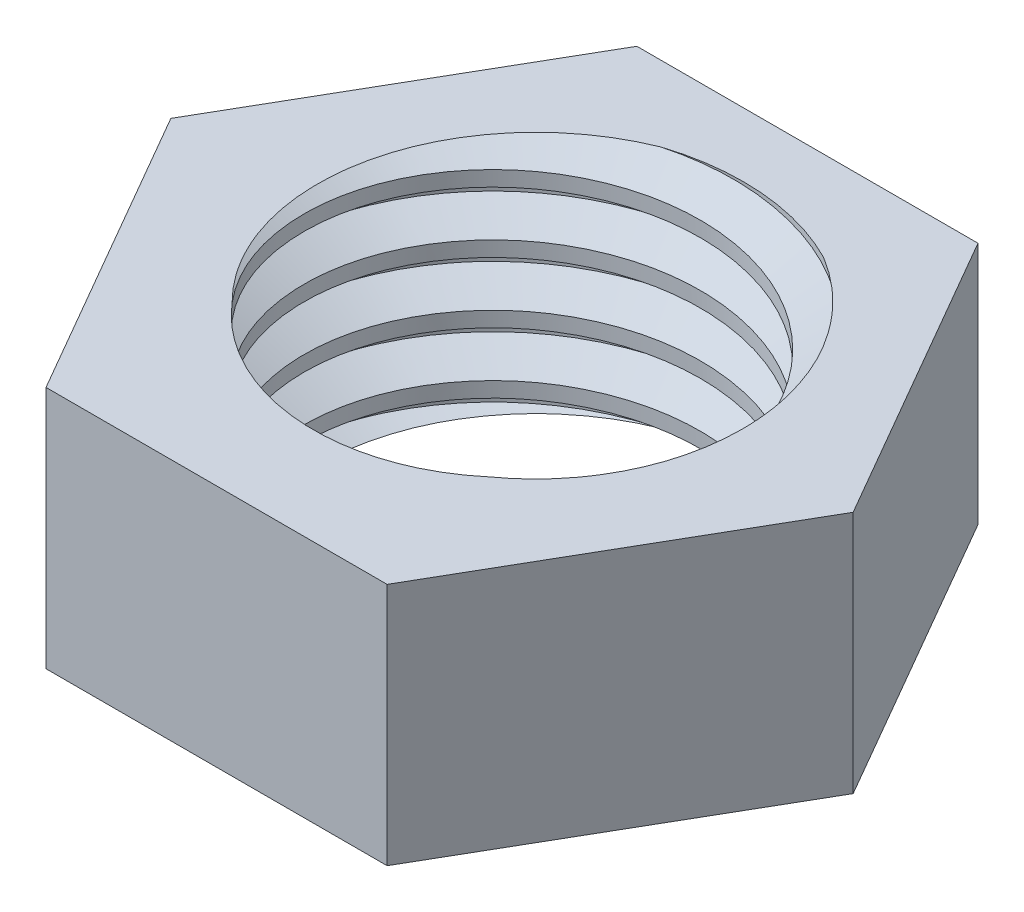
SolidWorks part; units mm, degrees
ref_plane "Front Plane" through (0, 0, 0) normal (0, 0, 1) x (1, 0, 0)
ref_plane "Top Plane" through (0, 0, 0) normal (0, 1, 0) x (1, 0, 0)
ref_plane "Right Plane" through (0, 0, 0) normal (1, 0, 0) x (0, 0, -1)
sketch "Sketch1" plane through (0, 0, 0) normal (0, 1, 0) x (1, 0, 0)
  line L1 (-7, 12.1244) -> (-14, 0)
  line L2 (-14, 0) -> (-7, -12.1244)
  line L3 (-7, -12.1244) -> (7, -12.1244)
  line L4 (7, -12.1244) -> (14, 0)
  line L5 (14, 0) -> (7, 12.1244)
  line L6 (7, 12.1244) -> (-7, 12.1244)
  circle A0 centre (0, 0) radius 12.1244 construction
  circle A1 centre (0, 0) radius 9.5
  dimension "D2" = 19
  dimension "D1" = 28
extrude "Boss-Extrude1" add sketch "Sketch1" along normal blind 10
thread "Thread1" pitch 2.5 method extrude trim with start face yes trim with end face yes profile "Thread Profile1" start angle 0, offset 3, length 0, pitch 2.5, diameter 19
ref_plane "Plane1" through (-9.5, 13, 0) normal (0, 0, 1) x (-1, 0, 0)
sketch "Thread Profile1" plane through (-9.5, 13, 0) normal (0, 0, 1) x (-1, 0, 0)
  line L0 (0, 0) -> (0, 2.5) construction
  line L11 (0, 0) -> (0, 2.1875)
  line L12 (0, 2.1875) -> (-1.3532, 1.4062)
  line L13 (-1.3532, 1.4062) -> (-1.3532, 0.7812)
  line L15 (-1.3532, 0.7812) -> (0, 0)
  line L17 (-1.3532, 1.0937) -> (0, 1.0937) construction
  point P2 (0, 0)
  dimension "Pitch" = 2.5
  dimension "Profile_Angle" = 60
  dimension "Profile_Land" = 0.625
  dimension "Profile_Height" = 1.3532
